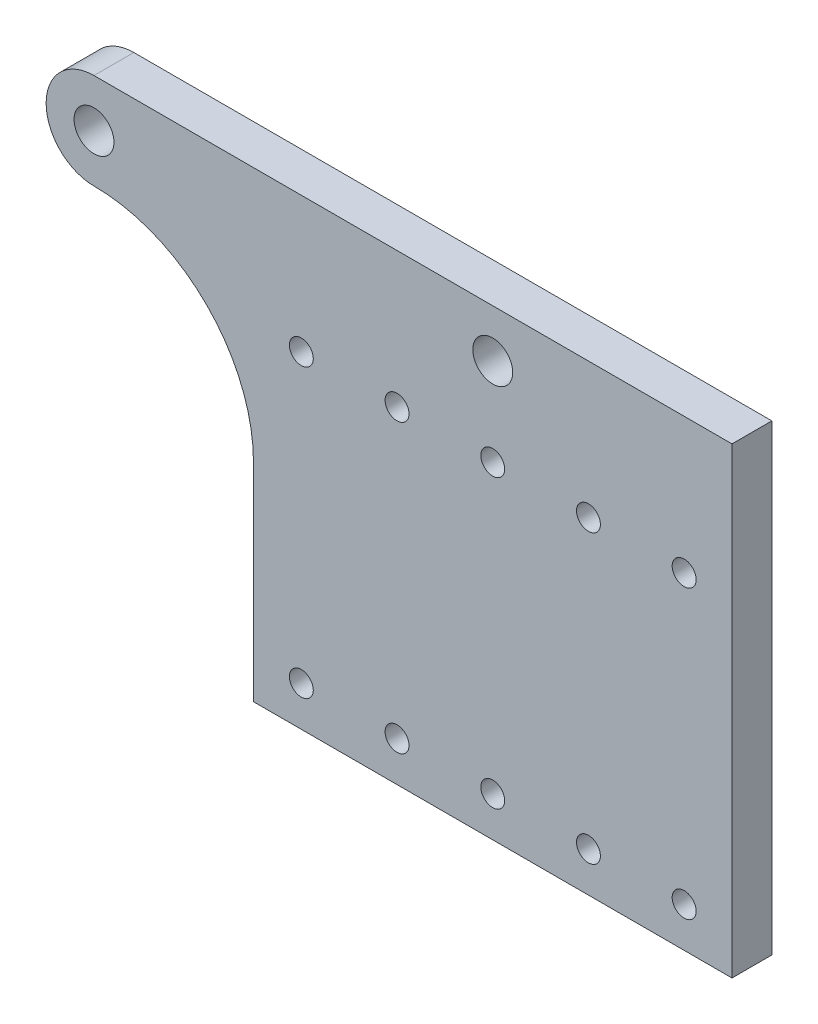
SolidWorks part; units mm, degrees
ref_plane "前基準面" through (0, 0, 0) normal (0, 0, 1) x (1, 0, 0)
ref_plane "上基準面" through (0, 0, 0) normal (0, 1, 0) x (1, 0, 0)
ref_plane "右基準面" through (0, 0, 0) normal (1, 0, 0) x (0, 0, -1)
sketch "草圖1" plane through (0, 0, 0) normal (0, 0, 1) x (1, 0, 0)
  line L2 (-30, 0) -> (-30, -46)
  line L3 (-30, -46) -> (30, -46)
  line L4 (30, 0) -> (30, -46)
  line L5 (-30, 0) -> (30, -46) construction
  line L6 (-30, -46) -> (30, 0) construction
  line L7 (-30, 0) -> (-50, 0)
  line L9 (-50, 12) -> (30, 12)
  line L11 (-50, 6) -> (0, 6) construction
  line L12 (30, 12) -> (30, 0)
  circle A2 centre (0, 6) radius 2.5
  circle A4 centre (-50, 6) radius 2.5
  arc A5 (-50, 12) -> (-50, 0) centre (-50, 6) ccw
  point P4 (0, -23)
  dimension "D1" = 6
  dimension "D2" = 5
  dimension "D6" = 12
  dimension "D3" = 60
  dimension "D4" = 46
  dimension "D5" = 50
extrude "填料-伸長1" add sketch "草圖1" along normal blind 5
sketch "草圖2" plane through (0, 0, 5) normal (0, 0, 1) x (1, 0, 0)
  line L0 (-30, 0) -> (-30, -46) construction
  line L2 (-50, 0) -> (-30, 0) construction
  circle A0 centre (-24, -5) radius 1.5
  circle A1 centre (-24, -41) radius 1.5
  dimension "D1" = 3
  dimension "D2" = 6
  dimension "D3" = 5
  dimension "D4" = 36
extrude "除料-伸長1" cut sketch "草圖2" against normal up to next
pattern_linear "直線複製排列1" count 5 spacing 12 along (1, 0, 0) of "除料-伸長1"
fillet "圓角1" radius 20 1 edges at (-30, 0, 2.5)
